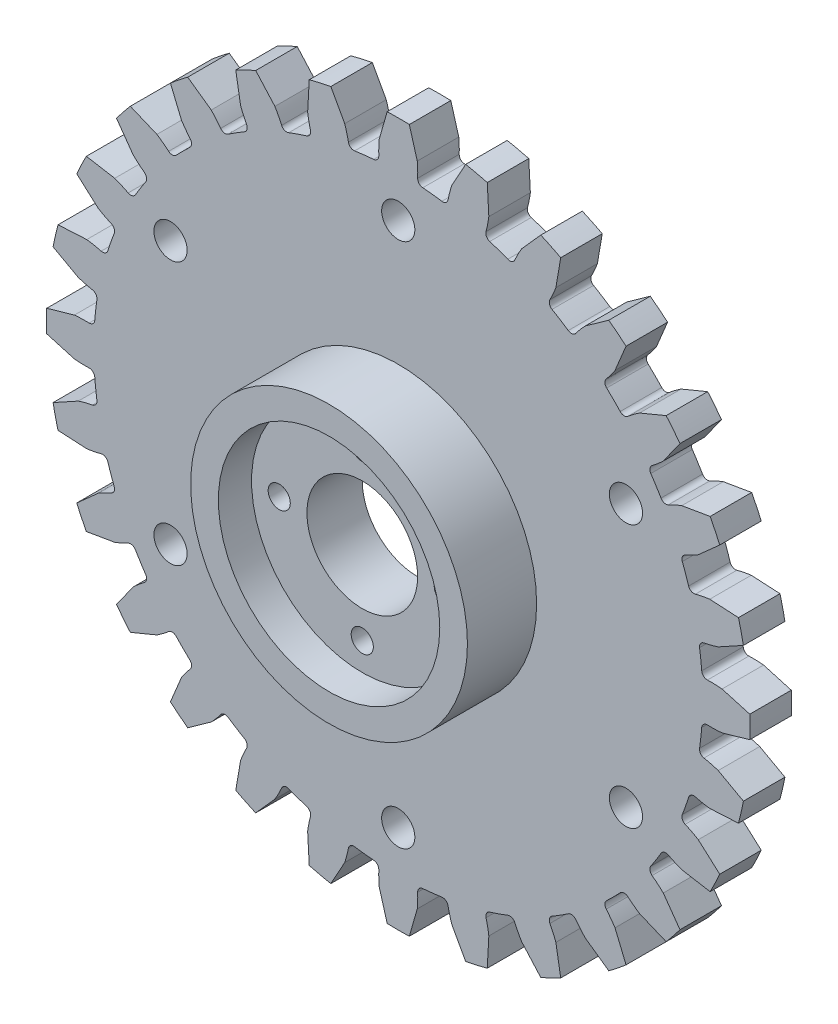
SolidWorks part; units mm, degrees
ref_plane "Front Plane" through (0, 0, 0) normal (0, 0, 1) x (1, 0, 0)
ref_plane "Top Plane" through (0, 0, 0) normal (0, 1, 0) x (1, 0, 0)
ref_plane "Right Plane" through (0, 0, 0) normal (1, 0, 0) x (0, 0, -1)
sketch "Sketch2" plane through (0, 0, 0) normal (0, 0, 1) x (1, 0, 0)
  circle A0 centre (0, 0) radius 110
  dimension "D1" = 220
extrude "Boss-Extrude1" add sketch "Sketch2" along normal blind 15
sketch "Sketch4" plane through (0, 0, 15) normal (0, 0, 1) x (1, 0, 0)
  line L1 (0, 127.063) -> (0, 0) construction
  line L2 (-4, 127) -> (-6.8675, 117)
  line L5 (4, 127) -> (6.8675, 117)
  circle A0 centre (0, 0) radius 110 construction
  arc A2 (-6.8675, 117) -> (-6.9245, 109.7818) centre (35, 113.06) ccw
  arc A4 (6.9245, 109.7818) -> (-6.9245, 109.7818) centre (0, 0) ccw
  arc A5 (6.8675, 117) -> (6.9245, 109.7818) centre (-35, 113.06) cw
  arc A6 (4, 127) -> (-4, 127) centre (0, 0) ccw
  dimension "D5" = 42.0524
  dimension "D6" = 35
  dimension "D1" = 16
  dimension "D3" = 127.063
  dimension "D2" = 8
  dimension "D4" = 10
extrude "Boss-Extrude2" add sketch "Sketch4" against normal up to surface (15 mm away) up to face at (110, 0, 0)
fillet "Fillet1" radius 2 2 edges at (-6.9245, 109.7818, 7.5) (6.9245, 109.7818, 7.5)
pattern_circular "CirPattern1" count 28 over 360 about axis through (0, 0, 15) along (0, 0, 1) of "Boss-Extrude2", "Fillet1"
hole_wizard "Ø12.0 (12) Diameter Hole1" positions "Sketch5" profile "Sketch6" hole size "Ø12.0" standard "ANSI Metric" end condition through all
sketch "Sketch5" plane through (0, 0, 15) normal (0, 0, 1) x (1, 0, 0)
  circle A0 centre (0, 0) radius 95 construction
  point P5 (0, 95)
  point P12 (82.2724, 47.5)
  point P13 (82.2724, -47.5)
  point P14 (0, -95)
  point P15 (-82.2724, -47.5)
  point P16 (-82.2724, 47.5)
  dimension "D1" = 190
  dimension "D2" = 6
sketch "Sketch6" plane through (-82.2724, 47.5, 15) normal (1, 0, 0) x (0, -1, 0)
  line L0 (0, 0) -> (0, 15)
  line L1 (0, 15) -> (6, 15)
  line L2 (6, 15) -> (6, 0)
  line L5 (6, 0) -> (0, 0)
  line L11 (0, -6.35) -> (0, 107.95) construction
  dimension "Thru Hole Dia." = 12
  dimension "Thru Hole Depth" = 15
sketch "Sketch7" plane through (0, 0, 15) normal (0, 0, 1) x (1, 0, 0)
  circle A0 centre (0, 0) radius 50
  circle A1 centre (0, 0) radius 40
  dimension "D1" = 100
  dimension "D2" = 80
extrude "Boss-Extrude3" add sketch "Sketch7" along normal blind 25
sketch "Sketch8" plane through (0, 0, 15) normal (0, 0, 1) x (1, 0, 0)
  circle A0 centre (0, 0) radius 20
  dimension "D1" = 40
extrude "Cut-Extrude1" cut sketch "Sketch8" against normal through all
sketch "Sketch9" plane through (0, 0, 0) normal (0, 0, -1) x (-1, 0, 0)
  circle A0 centre (0, 0) radius 40
  dimension "D1" = 80
extrude "Cut-Extrude2" cut sketch "Sketch9" against normal blind 8
hole_wizard "Ø8.0 (8) Diameter Hole1" positions "Sketch10" profile "Sketch11" hole size "Ø8.0" standard "ANSI Metric" end condition through all
sketch "Sketch10" plane through (0, 0, 8) normal (0, 0, -1) x (-1, 0, 0)
  circle A0 centre (0, 0) radius 30 construction
  point P9 (0, 30)
  point P15 (30, 0)
  point P16 (0, -30)
  point P17 (-30, 0)
  dimension "D1" = 60
  dimension "D2" = 4
sketch "Sketch11" plane through (30, 0, 8) normal (1, 0, 0) x (0, 1, 0)
  line L0 (0, 0) -> (0, 32)
  line L1 (0, 32) -> (4, 32)
  line L2 (4, 32) -> (4, 0)
  line L5 (4, 0) -> (0, 0)
  line L11 (0, -6.35) -> (0, 107.95) construction
  dimension "Thru Hole Dia." = 8
  dimension "Thru Hole Depth" = 32
sketch "Sketch12" plane through (0, 0, 15) normal (0, 0, 1) x (1, 0, 0)
  circle A0 centre (30, 0) radius 4 construction
  circle A1 centre (0, 0) radius 40
  circle A2 centre (0, 0) radius 40
  circle A3 centre (30, 0) radius 4
  circle A4 centre (0, 0) radius 20 construction
  circle A5 centre (0, -30) radius 4 construction
  circle A6 centre (-30, 0) radius 4 construction
  circle A7 centre (0, 30) radius 4 construction
  circle A8 centre (0, 0) radius 20
  circle A9 centre (0, -30) radius 4
  circle A10 centre (-30, 0) radius 4
  circle A11 centre (0, 30) radius 4
  dimension "D1" = 0
extrude "Boss-Extrude4" add sketch "Sketch12" along normal offset from surface (13 mm away) 12 up to face at (50, 0, 40)
